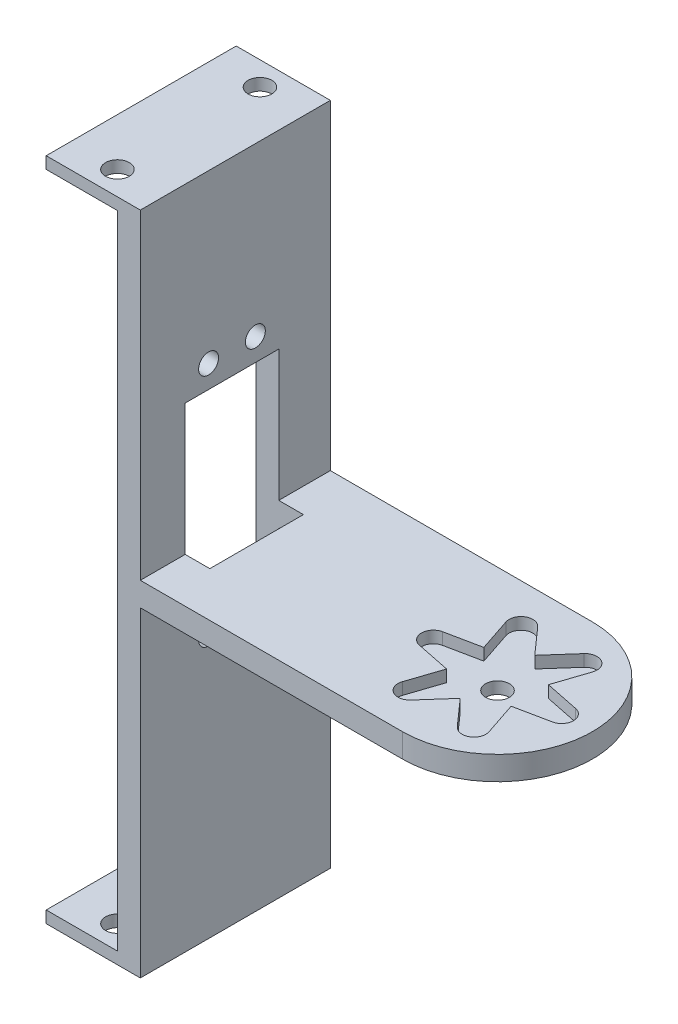
SolidWorks part; units mm, degrees
ref_plane "Front Plane" through (0, 0, 0) normal (0, 0, 1) x (1, 0, 0)
ref_plane "Top Plane" through (0, 0, 0) normal (0, 1, 0) x (1, 0, 0)
ref_plane "Right Plane" through (0, 0, 0) normal (1, 0, 0) x (0, 0, -1)
sketch "Sketch4" plane through (0, 0, 0) normal (0, 0, 1) x (1, 0, 0)
  line L0 (-19.7015, 42.1224) -> (-19.7015, -27.8776)
  line L1 (-14.8891, -27.8776) -> (60.2985, -27.8776)
  line L2 (60.2985, -27.8776) -> (60.2985, -22.8776)
  line L3 (60.2985, -22.8776) -> (-14.8891, -22.8776)
  line L8 (-19.7015, -27.8776) -> (-19.7015, -92.8776)
  line L10 (-14.8891, -95.3776) -> (-14.8891, -27.8776)
  line L21 (-14.8891, 44.6224) -> (-34.7015, 44.6224)
  line L22 (-34.7015, 44.6224) -> (-34.7015, 42.1224)
  line L23 (-34.7015, 42.1224) -> (-19.7015, 42.1224)
  line L27 (-14.8891, -95.3776) -> (-34.7015, -95.3776)
  line L28 (-34.7015, -95.3776) -> (-34.7015, -92.8776)
  line L29 (-34.7015, -92.8776) -> (-19.7015, -92.8776)
  line L31 (-14.8891, -22.8776) -> (-14.8891, 44.6224)
  point P2 (0, 0)
  point P7 (-15.751, 44.6224)
  dimension "D1" = 80
  dimension "D2" = 70
  dimension "D4" = 5
  dimension "D5" = 2.5
  dimension "D14" = 2.5
extrude "Boss-Extrude2" add sketch "Sketch4" along normal blind 40
fillet "Fillet3" 2 edges at (60.2985, -25.3776, 40) (60.2985, -25.3776, 0) type full round first side face at (-9.764, -25.3776, 40) second side face at (-9.764, -25.3776, 0) middle face at (60.2985, -25.3776, 20)
sketch "Sketch5" plane through (0, -22.8776, 0) normal (0, 1, 0) x (1, 0, 0)
  circle A0 centre (40.2985, -20) radius 2.5
extrude "Cut-Extrude2" cut sketch "Sketch5" against normal blind 40
sketch "Sketch6" plane through (-19.7015, 0, 0) normal (-1, 0, 0) x (0, 0, 1)
  line L0 (10.8558, 4.7096) -> (30.5558, 4.7096)
  line L1 (10.8558, 10.7596) -> (10.8558, 4.4096) construction
  line L2 (30.5558, 4.4096) -> (30.5558, 10.7596) construction
  line L3 (30.5558, 4.7096) -> (30.5558, -35.1904)
  line L4 (30.5558, -41.2404) -> (30.5558, -34.8904) construction
  line L5 (30.5558, -35.1904) -> (10.8558, -35.1904)
  line L6 (10.8558, -34.8904) -> (10.8558, -41.2404) construction
  line L7 (10.8558, -35.1904) -> (10.8558, 4.7096)
  circle A0 centre (15.7808, 9.4708) radius 2.1
  circle A1 centre (25.6308, 9.4708) radius 2.1
  circle A2 centre (15.7808, -39.9515) radius 2.1
  circle A3 centre (25.6308, -39.9515) radius 2.1
extrude "Cut-Extrude3" cut sketch "Sketch6" against normal blind 10
sketch "Sketch7" plane through (0, -22.8776, 0) normal (0, 1, 0) x (1, 0, 0)
  line L0 (35.4194, -6.6504) -> (40.2985, -12.155)
  line L1 (40.2985, -12.155) -> (45.1776, -6.6504)
  line L2 (49.42, -9.0997) -> (47.0924, -16.0775)
  line L3 (47.0924, -16.0775) -> (54.2992, -17.5506)
  line L4 (54.2992, -22.4494) -> (47.0924, -23.9225)
  line L5 (47.0924, -23.9225) -> (54.2992, -22.4494) construction
  line L6 (47.0924, -23.9225) -> (49.42, -30.9003)
  line L7 (45.1776, -33.3496) -> (40.2985, -27.845)
  line L8 (40.2985, -27.845) -> (35.4194, -33.3496)
  line L9 (31.177, -30.9003) -> (33.5046, -23.9225)
  line L10 (33.5046, -23.9225) -> (26.2978, -22.4494)
  line L11 (26.2978, -17.5506) -> (33.5046, -16.0775)
  line L12 (33.5046, -16.0775) -> (31.177, -9.0997)
  line L13 (31.177, -9.0997) -> (33.5046, -16.0775) construction
  arc A0 (35.4194, -6.6504) -> (31.177, -9.0997) centre (33.5485, -8.3087) ccw construction
  arc A1 (26.2978, -17.5506) -> (26.2978, -22.4494) centre (26.7985, -20) ccw
  arc A2 (31.177, -30.9003) -> (35.4194, -33.3496) centre (33.5485, -31.6913) ccw
  arc A3 (45.1776, -33.3496) -> (49.42, -30.9003) centre (47.0485, -31.6913) ccw
  arc A4 (54.2992, -22.4494) -> (54.2992, -17.5506) centre (53.7985, -20) ccw
  arc A5 (49.42, -9.0997) -> (45.1776, -6.6504) centre (47.0485, -8.3087) ccw
  arc A6 (31.177, -9.0997) -> (35.4194, -6.6504) centre (33.5485, -8.3087) cw
extrude "Cut-Extrude4" cut sketch "Sketch7" against normal blind 2.5
sketch "Sketch8" plane through (0, 22.1224, 0) normal (0, -1, 0) x (-1, 0, 0)
  circle A0 centre (24.7015, -5) radius 2.5
  circle A1 centre (24.7015, -35) radius 2.5
extrude "Cut-Extrude5" cut sketch "Sketch8" along normal blind 138 and the other way blind 49
